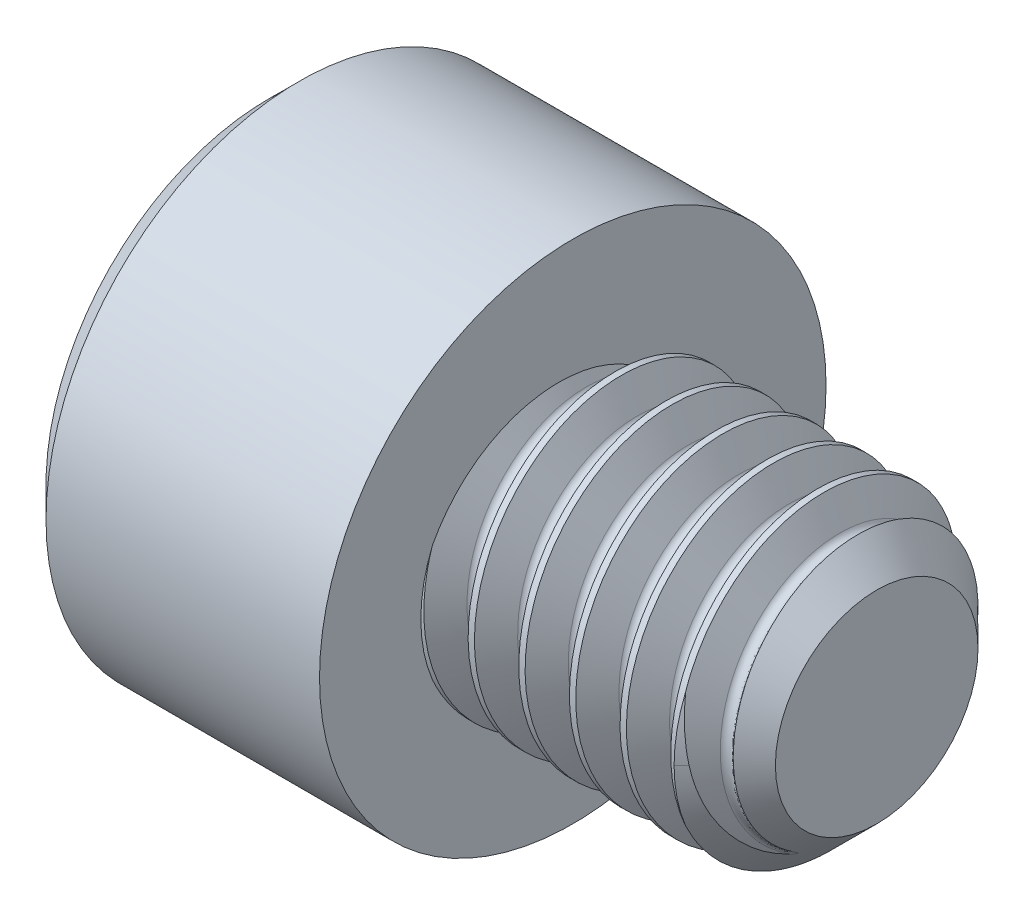
SolidWorks part; units mm, degrees
material "AISI Type 316L stainless steel"
ref_plane "Front Plane" through (0, 0, 0) normal (0, 0, 1) x (1, 0, 0)
ref_plane "Top Plane" through (0, 0, 0) normal (0, 1, 0) x (1, 0, 0)
ref_plane "Right Plane" through (0, 0, 0) normal (1, 0, 0) x (0, 0, -1)
sketch "Sketch1" plane through (0, 0, 0) normal (0, 0, 1) x (1, 0, 0)
  line L0 (-88.7055, 0) -> (96.9812, 0) construction
  line L1 (0, 0) -> (0, 5)
  line L2 (0, 5) -> (6, 5)
  line L4 (12, 0) -> (12, 3)
  line L5 (12, 3) -> (6, 3)
  line L6 (6, 3) -> (6, 5)
  line L7 (0, 0) -> (12, 0)
revolve "Revolve1" add sketch "Sketch1" angle 360 about L0
chamfer "Chamfer1" distance 1 angle 45 1 edges at (12, 0, 3)
chamfer "Chamfer2" distance 0.6 angle 45 1 edges at (0, 0, 5)
sketch "Sketch3" plane through (0, 0, 0) normal (1, 0, 0) x (0, 0, -1)
  line L1 (-2.8868, 0) -> (-1.4434, -2.5)
  line L2 (-1.4434, -2.5) -> (1.4434, -2.5)
  line L3 (1.4434, -2.5) -> (2.8868, 0)
  line L4 (2.8868, 0) -> (1.4434, 2.5)
  line L5 (1.4434, 2.5) -> (-1.4434, 2.5)
  line L6 (-1.4434, 2.5) -> (-2.8868, 0)
  circle A0 centre (0, 0) radius 2.5 construction
  dimension "D1" = 5
extrude "Cut-Extrude1" cut sketch "Sketch3" along normal blind 4
chamfer "Chamfer3" distance 0.6 angle 45 6 edges at (0, 2.5, 0) (0, 1.25, 2.1651) (0, -1.25, 2.1651) (0, -2.5, 0) (0, -1.25, -2.1651) (0, 1.25, -2.1651)
sketch "Sketch5" plane through (12, 0, 0) normal (1, 0, 0) x (0, 0, -1)
  circle A0 centre (0, 0) radius 3
curve "Helix/Spiral1" pitch 1 height 6 radius 3 centre (12, 0, 0) axis (-1, 0, 0) start towards (0, 0, -1)
sketch "Sketch8" plane through (0, 0, 0) normal (0, 1, 0) x (1, 0, 0)
  line L0 (12, 3) -> (12, 2.2423) construction
  line L1 (12.125, 2.4587) -> (12.6562, 3.3789)
  line L2 (12.6562, 3.3789) -> (11.3438, 3.3789)
  line L3 (11.3438, 3.3789) -> (11.875, 2.4587)
  line L4 (12, -2) -> (12, 2) construction
  circle A0 centre (12, 3) radius 0.3789 construction
  arc A1 (12.125, 2.4587) -> (11.875, 2.4587) centre (12, 2.5309) cw
  dimension "D2" = 0.1443
  dimension "D1" = 0.7578
sweep "Cut-Sweep1" cut profiles "Sketch8" path "Helix/Spiral1" align with end faces yes
